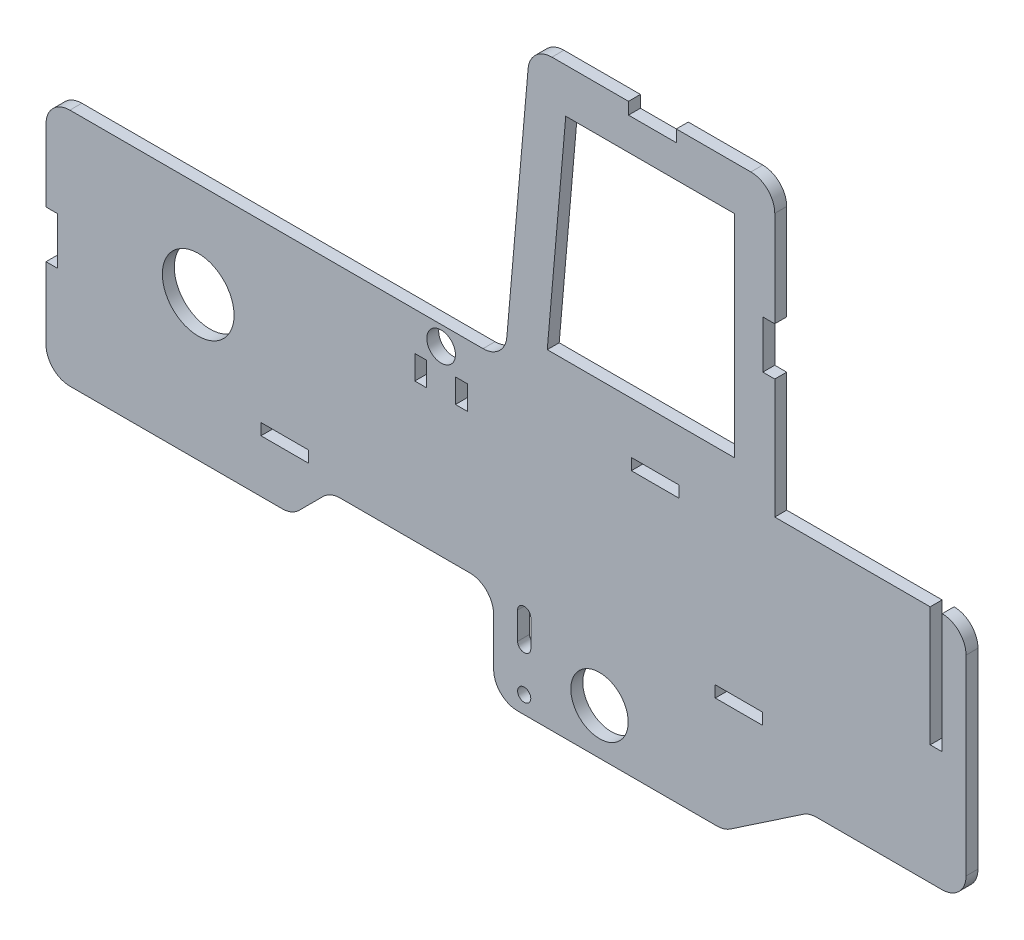
SolidWorks part; units mm, degrees
ref_plane "Front Plane" through (0, 0, 0) normal (0, 0, 1) x (1, 0, 0)
ref_plane "Top Plane" through (0, 0, 0) normal (0, 1, 0) x (1, 0, 0)
ref_plane "Right Plane" through (0, 0, 0) normal (1, 0, 0) x (0, 0, -1)
sketch "Sketch1" plane through (0, 0, 0) normal (0, 0, 1) x (1, 0, 0)
  line L0 (62.1239, 7.4217) -> (131.9663, 7.4217)
  line L1 (201.8088, 13.7717) -> (201.8088, 77.2717)
  line L2 (201.8088, 77.2717) -> (151.0088, 77.2717)
  line L3 (151.0088, 77.2717) -> (151.0088, 153.4717)
  line L4 (151.0088, 153.4717) -> (86.0089, 153.4717)
  line L5 (86.0089, 153.4717) -> (79.3423, 77.2717)
  line L6 (79.3423, 77.2717) -> (-42.5392, 77.2717)
  line L7 (-42.5392, 77.2717) -> (-42.5392, 13.7717)
  line L9 (-42.5392, 13.7717) -> (46.6174, 13.7717)
  line L10 (46.6174, 13.7717) -> (62.1239, 7.4217)
  line L11 (201.8088, 13.7717) -> (147.4729, 13.7717)
  line L12 (147.4729, 13.7717) -> (131.9663, 7.4217)
  dimension "D1" = 244.348
  dimension "D2" = 6.35
  dimension "D3" = 76.2
  dimension "D4" = 63.5
  dimension "D5" = 50.8
  dimension "D6" = 16.7564
  dimension "D7" = 16.7564
  dimension "D8" = 63.5
  dimension "D9" = 95
  dimension "D10" = 71.6665
extrude "Main Side" add sketch "Sketch1" along normal blind 3.175
sketch "Sketch2" plane through (0, 0, 3.175) normal (0, 0, 1) x (1, 0, 0)
  line L0 (-39.4912, 77.2717) -> (-39.4912, 13.7717) construction
  line L15 (79.3423, 77.2717) -> (-42.5392, 77.2717) construction
  line L16 (-42.5392, 77.2717) -> (-42.5392, 13.7717) construction
  line L26 (-39.4912, 18.5744) -> (201.8088, 18.5744) construction
  line L27 (201.8088, 13.7717) -> (201.8088, 77.2717) construction
  line L28 (81.1588, 18.5744) -> (81.1588, 153.4717) construction
  line L29 (151.0088, 153.4717) -> (86.0089, 153.4717) construction
  line L30 (81.1588, 36.7006) -> (201.8088, 36.7006) construction
  line L41 (62.1239, 7.4217) -> (131.9663, 7.4217) construction
  line L42 (135.1973, 30.7897) -> (147.7703, 30.7897)
  line L43 (135.1973, 30.7897) -> (135.1973, 27.7417)
  line L44 (135.1973, 27.7417) -> (147.7703, 27.7417)
  line L45 (147.7703, 30.7897) -> (147.7703, 27.7417)
  line L46 (14.5473, 30.7897) -> (14.5473, 27.7417)
  line L47 (27.1203, 27.7417) -> (14.5473, 27.7417)
  line L48 (27.1203, 30.7897) -> (27.1203, 27.7417)
  line L49 (27.1203, 30.7897) -> (14.5473, 30.7897)
  line L51 (-42.5392, 13.7717) -> (46.6174, 13.7717) construction
  point P20 (141.4838, 30.7897)
  point P21 (141.4838, 36.7006)
  dimension "D1" = 12.573
  dimension "D2" = 3.048
  dimension "D3" = 20.32
  dimension "D4" = 3.048
extrude "Bottom Plate Holes" cut sketch "Sketch2" against normal through all
sketch "Sketch3" plane through (0, 0, 3.175) normal (0, 0, 1) x (1, 0, 0)
  line L1 (112.9088, 71.9377) -> (125.6088, 71.9377)
  line L2 (112.9088, 71.9377) -> (112.9088, 68.8897)
  line L3 (112.9088, 68.8897) -> (125.6088, 68.8897)
  line L4 (125.6088, 71.9377) -> (125.6088, 68.8897)
  line L5 (201.8088, 13.7717) -> (201.8088, 77.2717) construction
  line L6 (147.7703, 30.7897) -> (135.1973, 30.7897) construction
  dimension "D1" = 12.7
  dimension "D2" = 3.048
  dimension "D3" = 38.1
  dimension "D4" = 76.2
extrude "Cut-Extrude1" cut sketch "Sketch3" against normal through all
sketch "Sketch4" plane through (0, 0, 3.175) normal (0, 0, 1) x (1, 0, 0)
  line L0 (-42.5392, 77.2717) -> (-42.5392, 13.7717) construction
  line L1 (-42.5392, 51.8082) -> (-39.4912, 51.8082)
  line L2 (-42.5392, 51.8082) -> (-42.5392, 39.2352)
  line L3 (-42.5392, 39.2352) -> (-39.4912, 39.2352)
  line L4 (-39.4912, 51.8082) -> (-39.4912, 39.2352)
  point P6 (-42.5392, 45.5217)
  point P7 (-42.5392, 45.5217)
  dimension "D1" = 3.048
  dimension "D2" = 12.573
extrude "Cut-Extrude2" cut sketch "Sketch4" against normal through all
sketch "Sketch5" plane through (0, 0, 3.175) normal (0, 0, 1) x (1, 0, 0)
  line L0 (201.8088, 77.2717) -> (151.0088, 77.2717) construction
  line L1 (192.2838, 77.2717) -> (195.4588, 77.2717)
  line L2 (192.2838, 77.2717) -> (192.2838, 45.5217)
  line L3 (192.2838, 45.5217) -> (195.4588, 45.5217)
  line L4 (195.4588, 77.2717) -> (195.4588, 45.5217)
  line L5 (201.8088, 13.7717) -> (201.8088, 77.2717) construction
  dimension "D1" = 3.175
  dimension "D2" = 31.75
  dimension "D3" = 6.35
extrude "Cut-Extrude3" cut sketch "Sketch5" against normal through all
sketch "Sketch6" plane through (0, 0, 3.175) normal (0, 0, 1) x (1, 0, 0)
  line L0 (-42.5392, 77.2717) -> (-42.5392, 51.8082) construction
  line L1 (79.3423, 77.2717) -> (-42.5392, 77.2717) construction
  circle A0 centre (-2.1142, 51.8567) radius 9.525
  dimension "D2" = 25.415
  dimension "D3" = 19.05
  dimension "D1" = 40.425
extrude "Cut-Extrude4" cut sketch "Sketch6" against normal through all
sketch "Sketch7" plane through (0, 0, 3.175) normal (0, 0, 1) x (1, 0, 0)
  line L0 (151.0088, 153.4717) -> (86.0089, 153.4717) construction
  line L1 (112.1588, 153.4717) -> (124.8588, 153.4717)
  line L2 (112.1588, 153.4717) -> (112.1588, 150.2967)
  line L3 (112.1588, 150.2967) -> (124.8588, 150.2967)
  line L4 (124.8588, 153.4717) -> (124.8588, 150.2967)
  point P6 (118.5088, 153.4717)
  point P7 (118.5088, 153.4717)
  dimension "D1" = 3.175
  dimension "D2" = 12.7
extrude "Cut-Extrude5" cut sketch "Sketch7" against normal through all
sketch "Sketch8" plane through (0, 0, 3.175) normal (0, 0, 1) x (1, 0, 0)
  line L0 (151.0088, 77.2717) -> (151.0088, 153.4717) construction
  line L1 (147.8338, 121.7217) -> (151.0088, 121.7217)
  line L2 (147.8338, 121.7217) -> (147.8338, 109.0217)
  line L3 (147.8338, 109.0217) -> (151.0088, 109.0217)
  line L4 (151.0088, 121.7217) -> (151.0088, 109.0217)
  point P6 (151.0088, 115.3717)
  point P7 (151.0088, 115.3717)
  dimension "D1" = 3.175
  dimension "D2" = 12.7
extrude "Cut-Extrude6" cut sketch "Sketch8" against normal through all
sketch "Sketch13" plane through (0, 0, 3.175) normal (0, 0, 1) x (1, 0, 0)
  line L1 (-42.5392, 13.7717) -> (46.6174, 13.7717) construction
  line L4 (147.4729, 13.7717) -> (201.8088, 13.7717) construction
  line L5 (33.9174, 13.7717) -> (56.4826, -1.4683)
  line L6 (56.4826, -1.4683) -> (137.6077, -1.4683)
  line L7 (137.6077, -1.4683) -> (160.1729, 13.7717)
  line L8 (33.9174, 13.7717) -> (46.6174, 13.7717)
  line L9 (46.6174, 13.7717) -> (62.1239, 7.4217)
  line L10 (62.1239, 7.4217) -> (131.9663, 7.4217)
  line L11 (131.9663, 7.4217) -> (147.4729, 13.7717)
  line L12 (147.4729, 13.7717) -> (160.1729, 13.7717)
  dimension "D1" = 8.89
  dimension "D2" = 12.7
  dimension "D3" = 12.7
  dimension "D4" = 145.966
  dimension "D5" = 145.966
extrude "Boss-Extrude2" add sketch "Sketch13" against normal blind 3.175
sketch "Sketch10" plane through (0, 0, 3.175) normal (0, 0, 1) x (1, 0, 0)
  line L0 (84.4608, 21.734) -> (84.4608, 14.5493) construction
  line L1 (86.2108, 21.734) -> (86.2108, 14.5493)
  line L2 (82.7108, 21.734) -> (82.7108, 14.5493)
  line L3 (84.4608, 18.1417) -> (84.4608, 3.1417) construction
  line L4 (-42.5392, 39.2352) -> (-42.5392, 13.7717) construction
  line L6 (56.4826, -1.4683) -> (137.6077, -1.4683) construction
  circle A0 centre (84.4608, 3.1417) radius 1.75
  arc A1 (86.2108, 21.734) -> (82.7108, 21.734) centre (84.4608, 21.734) ccw
  arc A2 (82.7108, 14.5493) -> (86.2108, 14.5493) centre (84.4608, 14.5493) ccw
  circle A3 centre (104.4608, 10.6417) radius 7.62
  point P4 (84.4608, 18.1417)
  point P13 (84.4608, 10.6417)
  dimension "D2" = 3.5
  dimension "D4" = 15.24
  dimension "D6" = 7.1848
  dimension "D1" = 15
  dimension "D3" = 3.5
  dimension "D5" = 20
  dimension "D7" = 127
  dimension "D8" = 4.61
extrude "Cut-Extrude7" cut sketch "Sketch10" against normal through all
fillet "Fillet1" radius 6.35 11 edges at (151.0088, 153.4717, 1.5875) (86.0089, 153.4717, 1.5875) (79.3423, 77.2717, 1.5875) (201.8088, 13.7717, 1.5875) (-42.5392, 13.7717, 1.5875) (201.8088, 77.2717, 1.5875) (-42.5392, 77.2717, 1.5875) (160.1729, 13.7717, 1.5875) (137.6077, -1.4683, 1.5875) (56.4826, -1.4683, 1.5875) (33.9174, 13.7717, 1.5875)
sketch "Sketch14" plane through (0, 0, 3.175) normal (0, 0, 1) x (1, 0, 0)
  line L0 (62.3905, 72.1917) -> (62.3905, 6.1517) construction
  line L1 (55.4055, 67.1117) -> (58.5805, 67.1117)
  line L2 (55.4055, 67.1117) -> (55.4055, 60.7617)
  line L3 (55.4055, 60.7617) -> (58.5805, 60.7617)
  line L4 (58.5805, 67.1117) -> (58.5805, 60.7617)
  line L5 (62.3905, 39.1717) -> (53.23, 39.1717) construction
  line L6 (66.2005, 67.1117) -> (66.2005, 60.7617)
  line L7 (69.3755, 60.7617) -> (66.2005, 60.7617)
  line L8 (69.3755, 67.1117) -> (69.3755, 60.7617)
  line L9 (69.3755, 67.1117) -> (66.2005, 67.1117)
  line L10 (69.3755, 17.5817) -> (66.2005, 17.5817)
  line L11 (69.3755, 11.2317) -> (69.3755, 17.5817)
  line L12 (69.3755, 11.2317) -> (66.2005, 11.2317)
  line L13 (66.2005, 11.2317) -> (66.2005, 17.5817)
  line L14 (58.5805, 11.2317) -> (58.5805, 17.5817)
  line L15 (55.4055, 17.5817) -> (58.5805, 17.5817)
  line L16 (55.4055, 11.2317) -> (55.4055, 17.5817)
  line L17 (55.4055, 11.2317) -> (58.5805, 11.2317)
  line L18 (73.5236, 77.2717) -> (-36.1892, 77.2717) construction
  line L19 (58.4261, -1.4683) -> (135.6642, -1.4683) construction
  circle A0 centre (62.3905, 6.1517) radius 3.81
  circle A1 centre (62.3905, 72.1917) radius 3.81
  dimension "D1" = 7.62
  dimension "D2" = 3.175
  dimension "D3" = 6.35
  dimension "D4" = 3.81
  dimension "D5" = 5.08
  dimension "D6" = 5.08
  dimension "D7" = 7.62
extrude "Cut-Extrude8" cut sketch "Sketch14" against normal through all
sketch "Sketch15" plane through (0, 0, 3.175) normal (0, 0, 1) x (1, 0, 0)
  line L0 (90.5852, 85.5631) -> (95.4981, 141.7173)
  line L1 (95.4981, 141.7173) -> (140.3421, 141.7173)
  line L2 (140.3421, 141.7173) -> (140.3421, 85.5631)
  line L3 (140.3421, 85.5631) -> (90.5852, 85.5631)
  line L4 (151.0088, 121.7217) -> (151.0088, 147.1217) construction
  line L5 (58.4261, -1.4683) -> (135.6642, -1.4683) construction
  line L6 (112.1588, 153.4717) -> (91.8276, 153.4717) construction
  dimension "D1" = 95
  dimension "D2" = 10.6667
  dimension "D3" = 87.0314
  dimension "D4" = 11.7543
extrude "Cut-Extrude9" cut sketch "Sketch15" against normal through all
sketch "Sketch16" plane through (0, 0, 3.175) normal (0, 0, 1) x (1, 0, 0)
  line L0 (58.4261, -1.4683) -> (135.6642, -1.4683) construction
  line L1 (32.9631, 23.9317) -> (76.3485, 23.9317)
  line L2 (32.9631, 12.5342) -> (32.9631, -1.4683)
  line L3 (32.9631, -1.4683) -> (76.3485, -1.4683)
  line L4 (76.3485, 23.9317) -> (76.3485, -1.4683)
  line L5 (-42.5392, 39.2352) -> (-42.5392, 20.1217) construction
  line L6 (32.9631, 23.9317) -> (21.5657, 12.5342)
  line L7 (21.5657, 12.5342) -> (32.9631, 12.5342)
  dimension "D1" = 43.3854
  dimension "D2" = 75.5023
  dimension "D3" = 25.4
  dimension "D4" = 45
extrude "Cut-Extrude10" cut sketch "Sketch16" against normal through all
fillet "Fillet2" radius 6.35 4 edges at (22.8031, 13.7717, 1.5875) (32.9631, 23.9317, 1.5875) (76.3485, 23.9317, 1.5875) (76.3485, -1.4683, 1.5875)
